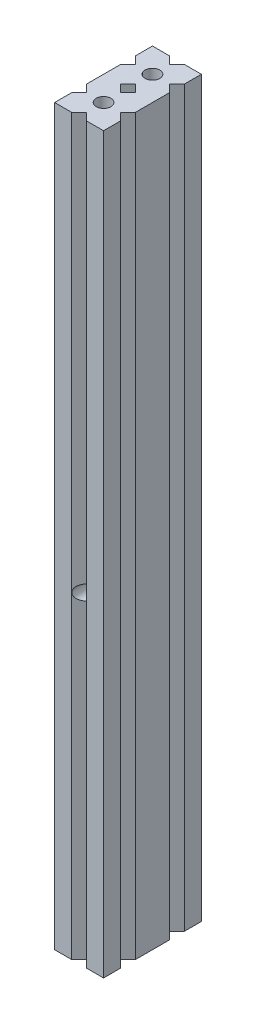
SolidWorks part; units mm, degrees
ref_plane "Front" through (0, 0, 0) normal (0, 0, 1) x (1, 0, 0)
ref_plane "Top" through (0, 0, 0) normal (0, 1, 0) x (1, 0, 0)
ref_plane "Right" through (0, 0, 0) normal (1, 0, 0) x (0, 0, -1)
sketch "Skizze1" plane through (0, 0, 0) normal (0, 1, 0) x (1, 0, 0)
  line L0 (0, 0) -> (0, 40)
  line L1 (0, 40) -> (20, 40)
  line L2 (20, 40) -> (20, 0)
  line L3 (20, 0) -> (0, 0)
  dimension "D1" = 20
  dimension "D2" = 40
extrude "Aufsatz-Linear austragen1" add sketch "Skizze1" along normal blind 300
sketch "Skizze2" plane through (0, 300, 0) normal (0, 1, 0) x (1, 0, 0)
  line L0 (10, 40) -> (10, 20) construction
  line L1 (0, 30) -> (20, 30) construction
  line L2 (7, 40) -> (10, 37)
  line L3 (13, 40) -> (10, 37)
  line L4 (10, 30) -> (20, 40) construction
  line L5 (7, 40) -> (13, 40)
  line L6 (20, 33) -> (17, 30)
  line L7 (20, 27) -> (17, 30)
  line L8 (20, 27) -> (20, 33)
  line L9 (0, 27) -> (0, 33)
  line L10 (0, 27) -> (3, 30)
  line L11 (0, 33) -> (3, 30)
  line L12 (7, 20) -> (13, 20)
  line L13 (13, 20) -> (10, 23)
  line L14 (7, 20) -> (10, 23)
  line L15 (0, 20) -> (20, 20) construction
  line L16 (0, 40) -> (0, 0) construction
  line L17 (20, 0) -> (20, 40) construction
  line L18 (20, 40) -> (0, 40) construction
  line L19 (7, 20) -> (10, 17)
  line L20 (13, 20) -> (10, 17)
  line L21 (20, 13) -> (17, 10)
  line L22 (20, 7) -> (17, 10)
  line L23 (20, 13) -> (20, 7)
  line L24 (13, 0) -> (10, 3)
  line L25 (7, 0) -> (13, 0)
  line L26 (7, 0) -> (10, 3)
  line L27 (0, 13) -> (3, 10)
  line L28 (0, 13) -> (0, 7)
  line L29 (0, 7) -> (3, 10)
  line M14 (0, 0) -> (20, 0)
  line M15 (20, 0) -> (20, 40)
  line M16 (20, 40) -> (0, 40)
  line M17 (0, 40) -> (0, 0)
  dimension "D1" = 3
  dimension "D2" = 3
extrude "Schnitt-Linear austragen1" cut sketch "Skizze2" against normal through all contours L11 L10 M17 | L3 L2 M16 | L7 L6 M15 | L20 L12 L19 | L14 L12 L13 | L22 L21 M15 | L29 L27 M17 | L26 L24 M14 region at (10, 300, -39) region at (1, 300, -30) region at (19, 300, -30) region at (1, 300, -10) region at (19, 300, -10) region at (10, 300, -1) region at (10, 300, -21) region at (10, 300, -19)
ref_plane "Ebene1" through (0, 150, 0) normal (0, 1, 0) x (1, 0, 0)
sketch "Skizze3" plane through (0, 0, 0) normal (0, -1, 0) x (1, 0, 0)
  line L0 (10, -3) -> (10, -17) construction
  line L1 (20, -20) -> (0, -20) construction
  line L2 (20, -13) -> (20, -27) construction
  line L3 (0, -27) -> (0, -13) construction
  circle A0 centre (10, -10) radius 3
  circle A1 centre (10, -30) radius 3
  dimension "D1" = 6
extrude "Schnitt-Linear austragen2" cut sketch "Skizze3" against normal through all
sketch "Sketch1" plane through (0, 0, 0) normal (0, 0, 1) x (1, 0, 0)
  line L0 (10, 0) -> (10, 300) construction
  line L1 (13, 0) -> (20, 0) construction
  circle A0 centre (10, 130) radius 3
  dimension "D1" = 6
  dimension "D2" = 130
extrude "Extrude1" cut sketch "Sketch1" against normal blind 40
